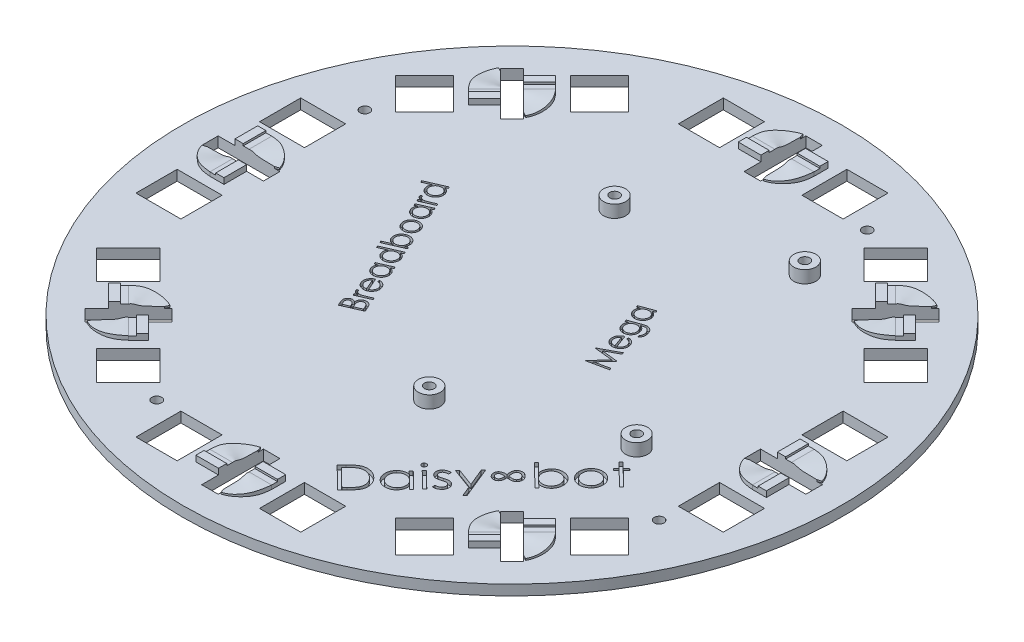
SolidWorks part; units mm, degrees
ref_plane "Front" through (0, 0, 0) normal (0, 0, 1) x (1, 0, 0)
ref_plane "Top" through (0, 0, 0) normal (0, 1, 0) x (1, 0, 0)
ref_plane "Right" through (0, 0, 0) normal (1, 0, 0) x (0, 0, -1)
sketch "Sketch1" plane through (0, 0, 0) normal (0, 1, 0) x (1, 0, 0)
  circle A0 centre (0, 0) radius 101.6
  dimension "D1" = 203.2
extrude "Boss-Extrude1" add sketch "Sketch1" along normal blind 3.175 contours A0
sketch "Sketch2" plane through (0, 3.175, 0) normal (0, 1, 0) x (1, 0, 0)
  line L1 (-2.54, -93.1333) -> (2.54, -93.1333)
  line L2 (-2.54, -93.1333) -> (-2.54, -74.0833)
  line L3 (-2.54, -74.0833) -> (2.54, -74.0833)
  line L4 (2.54, -93.1333) -> (2.54, -74.0833)
  point P4 (0, -74.0833)
  dimension "D1" = 5.08
  dimension "D2" = 19.05
  dimension "D3" = 93.1333
extrude "Cut-Extrude1" cut sketch "Sketch2" against normal up to next and the other way through all contours L1 L4 L3 L2
sketch "Sketch4" plane through (0, 3.175, 0) normal (0, 1, 0) x (1, 0, 0)
  line L0 (0, -83.6083) -> (-2.9434, -74.5495) construction
  line L1 (-2.9434, -74.5495) -> (0, -83.6083) construction
  line L2 (0, -83.6083) -> (-5.5987, -75.9024) construction
  line L3 (0, -83.6083) -> (-7.7059, -78.0097) construction
  line L4 (0, -83.6083) -> (-9.0588, -80.6649) construction
  line L5 (0, -83.6083) -> (-9.525, -83.6083) construction
  line L9 (2.54, -74.0833) -> (-2.54, -74.0833) construction
  line L10 (2.54, -74.0833) -> (2.54, -93.1333) construction
  line L11 (-2.54, -74.0833) -> (-2.54, -93.1333) construction
  line L12 (2.54, -93.1333) -> (-2.54, -93.1333) construction
  circle A0 centre (0, -83.6083) radius 9.525 construction
  point P16 (0, -74.0833)
  point P19 (2.54, -83.6083)
  dimension "D1" = 18
  dimension "D2" = 18
  dimension "D3" = 18
  dimension "D4" = 18
  dimension "D5" = 18
ref_plane "Plane1" through (-24.5719, 0, 7.9839) normal (0.9511, 0, -0.309) x (-0.309, 0, -0.9511)
ref_plane "Plane2" through (-39.7581, 0, 28.886) normal (0.809, 0, -0.5878) x (-0.5878, 0, -0.809)
ref_plane "Plane3" through (-39.7581, 0, 54.7224) normal (0.5878, 0, -0.809) x (-0.809, 0, -0.5878)
ref_plane "Plane4" through (-24.5719, 0, 75.6244) normal (0.309, 0, -0.9511) x (-0.9511, 0, -0.309)
ref_plane "Plane5" through (0, 0, 83.6083) normal (0, 0, -1) x (-1, 0, 0)
sketch "Sketch5" plane through (-24.5719, 0, 7.9839) normal (0.9511, 0, -0.309) x (-0.309, 0, -0.9511)
  line L0 (-69.6725, 3.175) -> (-87.7902, 3.175) construction
  line L1 (-71.2966, 3.175) -> (-69.9913, 3.175)
  line L2 (-71.2966, 3.175) -> (-71.2966, 3.683)
  line L3 (-71.2966, 3.683) -> (-69.9913, 3.683)
  line L4 (-69.9913, 3.175) -> (-69.9913, 3.683)
  dimension "D2" = 0.508
sketch "Sketch6" plane through (-39.7581, 0, 28.886) normal (0.809, 0, -0.5878) x (-0.5878, 0, -0.809)
  line L0 (-58.4417, 3.175) -> (-73.8535, 3.175) construction
  line L1 (-63.3193, 3.175) -> (-58.1156, 3.175)
  line L2 (-63.3193, 3.175) -> (-63.3193, 3.775)
  line L3 (-63.3193, 3.775) -> (-58.1156, 3.775)
  line L4 (-58.1156, 3.175) -> (-58.1156, 3.775)
  dimension "D2" = 0.6
sketch "Sketch7" plane through (-39.7581, 0, 54.7224) normal (0.5878, 0, -0.809) x (-0.809, 0, -0.5878)
  line L0 (-41.4902, 3.175) -> (-52.6875, 3.175) construction
  line L1 (-46.0041, 3.175) -> (-39.6187, 3.175)
  line L2 (-46.0041, 3.175) -> (-46.0041, 4.075)
  line L3 (-46.0041, 4.075) -> (-39.6187, 4.075)
  line L4 (-39.6187, 3.175) -> (-39.6187, 4.075)
  dimension "D2" = 0.9
sketch "Sketch10" plane through (-24.5719, 0, 75.6244) normal (0.309, 0, -0.9511) x (-0.9511, 0, -0.309)
  line L0 (-25.8364, 3.175) -> (-16.7776, 3.175) construction
  line L1 (-23.1657, 3.175) -> (-16.3114, 3.175)
  line L2 (-23.1657, 3.175) -> (-23.1657, 4.375)
  line L3 (-23.1657, 4.375) -> (-16.3114, 4.375)
  line L4 (-16.3114, 3.175) -> (-16.3114, 4.375)
  dimension "D3" = 1.2
sketch "Sketch11" plane through (0, 0, 83.6083) normal (0, 0, -1) x (-1, 0, 0)
  line L0 (0, 3.175) -> (9.525, 3.175) construction
  line L1 (2.54, 3.175) -> (9.525, 3.175)
  line L2 (2.54, 3.175) -> (2.54, 4.375)
  line L3 (2.54, 4.375) -> (9.525, 4.375)
  line L4 (9.525, 3.175) -> (9.525, 4.375)
  dimension "D3" = 1.2
loft "Loft1" add profiles "Sketch5", "Sketch6", "Sketch7", "Sketch10", "Sketch11" connector at (-2.54, 3.683, 75.791) connector at (-2.54, 3.775, 80.1123) connector at (-2.54, 4.075, 81.7629) connector at (-2.54, 4.375, 82.783) connector at (-2.54, 4.375, 83.6083)
sketch "Sketch13" plane through (-104.9799, 0, 83.6083) normal (0, 0, -1) x (-1, 0, 0)
  line L6 (-95.4549, 3.175) -> (-102.4399, 3.175)
  line L7 (-95.4549, 3.175) -> (-95.4549, 4.375)
  line L8 (-95.4549, 4.375) -> (-102.4399, 4.375)
  line L9 (-102.4399, 3.175) -> (-102.4399, 4.375)
extrude "Boss-Extrude4" add sketch "Sketch13" against normal blind 1.7907
sketch "Sketch25" plane through (0, 0, 85.399) normal (0, 0, 1) x (1, 0, 0)
  line L0 (-9.525, 4.375) -> (-2.54, 4.375) construction
  line L1 (-9.525, 3.175) -> (-2.54, 3.175)
  line L2 (-9.525, 3.175) -> (-9.525, 4.975)
  line L3 (-9.525, 4.975) -> (-2.54, 4.975)
  line L4 (-2.54, 3.175) -> (-2.54, 4.975)
  dimension "D1" = 0.6
extrude "Boss-Extrude5" add sketch "Sketch25" along normal blind 2.54
sketch "Sketch14" plane through (-2.54, 0, 0) normal (1, 0, 0) x (0, 0, -1)
  line L0 (-83.6083, 3.175) -> (-83.6083, 0) construction
  line L1 (-74.0833, 0) -> (-93.1333, 0) construction
ref_plane "Plane6" through (0, 0, 0) normal (1, 0, 0) x (0, 0, -1)
sketch "Sketch15" plane through (0, 0, 0) normal (1, 0, 0) x (0, 0, -1)
  line L0 (-83.6083, 0) -> (-83.6083, 3.175) construction
pattern_circular "CirPattern1" count 2 over 360 about axis through (0, 0, 83.6083) along (0, 1, 0) of "Loft1", "Boss-Extrude5", "Boss-Extrude4" reverse direction yes
ref_axis "Axis1" through (0, 50, 0) along (0, -1, 0)
pattern_circular "CirPattern5" count 8 over 360 about axis through (0, 50, 0) along (0, -1, 0) of "CirPattern1", "Cut-Extrude1"
sketch "Sketch18" plane through (0, 3.175, 0) normal (0, 1, 0) x (1, 0, 0)
  line L0 (-12.3739, 44.0137) -> (34.085, 57.075) construction
  line L1 (-12.3739, 44.0137) -> (9.9679, -35.4555) construction
  line L2 (34.085, 57.075) -> (34.4287, 55.8524) construction
  line L3 (54.7082, -16.2811) -> (8.2493, -29.3425) construction
  line L4 (0, -101.6) -> (0, 101.6) construction
  line L5 (0, -1.7463) -> (0, 1.7463) construction
  line L6 (-101.6, 0) -> (101.6, 0) construction
  line L7 (34.4287, 55.8524) -> (54.7082, -16.2811) construction
  circle A0 centre (-12.3739, 44.0137) radius 3.405
  circle A1 centre (9.9679, -35.4555) radius 3.405
  circle A2 centre (54.7082, -16.2811) radius 3.405
  circle A3 centre (34.4287, 55.8524) radius 3.405
  circle A4 centre (9.9679, -35.4555) radius 1.5
  circle A5 centre (-12.3739, 44.0137) radius 1.5
  circle A6 centre (34.4287, 55.8524) radius 1.5
  circle A7 centre (54.7082, -16.2811) radius 1.5
  circle A8 centre (0, 0) radius 101.6 construction
  dimension "D7" = 1.905
  dimension "D8" = 3
  dimension "D9" = 1.27
  dimension "D1" = 82.55
  dimension "D2" = 74.93
  dimension "D4" = 15.703
  dimension "D5" = 36.83
  dimension "D10" = 48.26
sketch "Sketch19" plane through (0, 3.175, 0) normal (0, 1, 0) x (1, 0, 0)
  line L0 (-32.0765, -77.4396) -> (0, 0) construction
  line L1 (0, -101.6) -> (0, 101.6) construction
  circle A1 centre (-32.0765, -77.4396) radius 1.5
  circle A4 centre (0, 0) radius 101.6 construction
  dimension "D4" = 3
  dimension "D6" = 83.82
  dimension "D5" = 22.5
extrude "Cut-Extrude2" cut sketch "Sketch19" against normal through all
pattern_circular "CirPattern7" count 4 over 360 about axis through (0, 50, 0) along (0, -1, 0) of "Cut-Extrude2"
extrude "Boss-Extrude3" add sketch "Sketch18" along normal blind 3.81
sketch "Sketch23" plane through (0, 3.175, 0) normal (0, 1, 0) x (1, 0, 0)
  line L9 (-2.54, -87.939) -> (-2.54, -93.1333) construction
  line L10 (-25.4, -76.6805) -> (-12.7, -76.6805)
  line L11 (-25.4, -76.6805) -> (-25.4, -90.5362)
  line L16 (-25.4, -90.5362) -> (-12.7, -90.5362)
  line L17 (-12.7, -76.6805) -> (-12.7, -90.5362)
  line L19 (2.54, -74.0833) -> (2.54, -79.2776) construction
  line L20 (0, -50) -> (0, 50) construction
  line L21 (12.7, -76.6805) -> (12.7, -90.5362)
  line L22 (25.4, -90.5362) -> (12.7, -90.5362)
  line L23 (25.4, -76.6805) -> (25.4, -90.5362)
  line L24 (25.4, -76.6805) -> (12.7, -76.6805)
  point P8 (-2.54, -90.5362)
  point P9 (2.54, -76.6805)
  dimension "D1" = 12.7
  dimension "D2" = 10.16
extrude "Cut-Extrude6" cut sketch "Sketch23" against normal through all
pattern_circular "CirPattern8" count 8 over 360 about axis through (0, 50, 0) along (0, -1, 0) of "Cut-Extrude6"
sketch "Sketch17" plane through (0, 3.175, 0) normal (0, 1, 0) x (1, 0, 0)
  line L0 (19.0413, -74.398) -> (63.1398, -28.708) construction
  dimension "D2" = 74.398
  dimension "D1" = 63.5
  dimension "D3" = 69.3598
  dimension "D4" = 76.796
sketch "Sketch16" plane through (0, 3.175, 0) normal (0, 1, 0) x (1, 0, 0)
  line L0 (19.0413, -74.398) -> (63.1398, -28.708) construction
  line L1 (25.4, -76.6805) -> (12.7, -76.6805) construction
  text T0 "Daisy∞bot\r\n" font "Century Gothic" height in points 36
extrude "Cut-Extrude4" cut sketch "Sketch16" against normal blind 1.27
sketch "Sketch22" plane through (0, 3.175, 0) normal (0, 1, 0) x (1, 0, 0)
  line L0 (-44.1287, 25.1735) -> (-20.5694, -28.6741) construction
  text T0 "Breadboard"
extrude "Cut-Extrude5" cut sketch "Sketch22" against normal blind 1.27
sketch "Sketch24" plane through (0, 3.175, 0) normal (0, 1, 0) x (1, 0, 0)
  line L0 (29.8571, 0) -> (21.0896, 23.8389) construction
  text T0 "Mega"
  dimension "D1" = 28.022
  dimension "D2" = 25.4
  dimension "D3" = 29.8571
extrude "Cut-Extrude7" cut sketch "Sketch24" against normal blind 1.27
